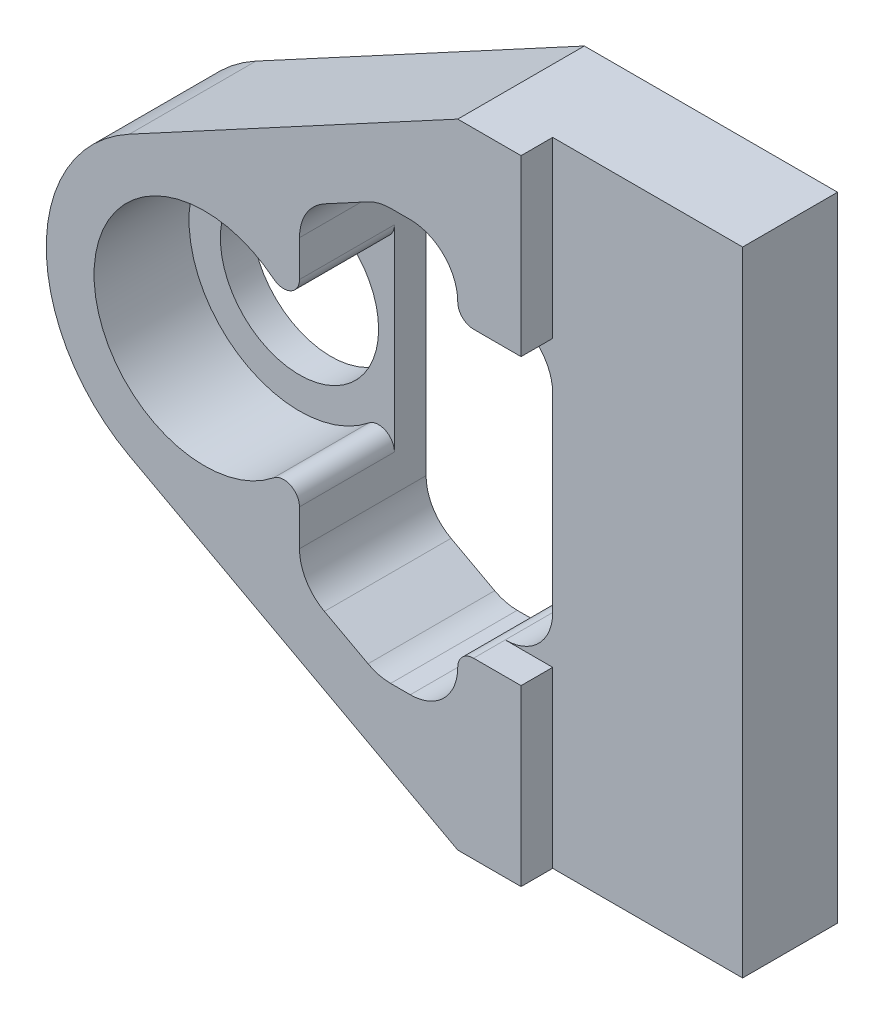
SolidWorks part; units mm, degrees
ref_plane "Front Plane" through (0, 0, 0) normal (0, 0, 1) x (1, 0, 0)
ref_plane "Top Plane" through (0, 0, 0) normal (0, 1, 0) x (1, 0, 0)
ref_plane "Right Plane" through (0, 0, 0) normal (1, 0, 0) x (0, 0, -1)
sketch "Sketch1" plane through (0, 0, 0) normal (0, 0, 1) x (1, 0, 0)
  line L0 (-2.3749, 4.4) -> (8, 10)
  line L1 (8, -10) -> (16, -10)
  line L2 (8, -10) -> (-2.3749, -4.4)
  line L3 (8, 10) -> (16, 10)
  line L4 (16, -10) -> (16, 10)
  circle A0 centre (0, 0) radius 2.5
  arc A1 (-2.3749, 4.4) -> (-2.3749, -4.4) centre (0, 0) ccw
  dimension "D5" = 5
  dimension "D2" = 5
  dimension "D1" = 16
  dimension "D3" = 8
  dimension "D4" = 10
  dimension "D6" = 10
extrude "Boss-Extrude1" add sketch "Sketch1" along normal blind 4
sketch "Sketch4" plane through (0, 0, 4) normal (0, 0, 1) x (1, 0, 0)
  circle A0 centre (0, 0) radius 3.49
  dimension "D1" = 6.98
extrude "Cut-Extrude1" cut sketch "Sketch4" against normal blind 3
sketch "Sketch5" plane through (0, 0, 4) normal (0, 0, 1) x (1, 0, 0)
  line L0 (8, -10) -> (16, -10) construction
  line L1 (16, 10) -> (10, 10)
  line L2 (16, 10) -> (16, -10)
  line L3 (16, -10) -> (10, -10)
  line L4 (10, 10) -> (10, -10)
  dimension "D1" = 6
extrude "Cut-Extrude2" cut sketch "Sketch5" against normal blind 1
sketch "Sketch6" plane through (0, 0, 4) normal (0, 0, 1) x (1, 0, 0)
  line L0 (3, 5.1506) -> (5.5, 6.5)
  line L1 (5.5, 6.5) -> (8, 6.5)
  line L2 (3, 5.1506) -> (3, -5.1506)
  line L3 (5.5, -6.5) -> (8, -6.5)
  line L4 (8, -4.5) -> (8, -6.5)
  line L5 (3, -5.1506) -> (5.5, -6.5)
  line L6 (8, 10) -> (-2.3749, 4.4) construction
  line L7 (8, -4.5) -> (10, -4.5)
  line L8 (10, 10) -> (10, -10) construction
  line L9 (10, -4.5) -> (10, 4.5)
  line L10 (10, 10) -> (10, -10) construction
  line L11 (10, 4.5) -> (8, 4.5)
  line L12 (8, 4.5) -> (8, 6.5)
  dimension "D1" = 3
  dimension "D2" = 5
  dimension "D3" = 6.5
  dimension "D4" = 13
  dimension "D5" = 2.5
  dimension "D6" = 9
extrude "Cut-Extrude3" cut sketch "Sketch6" against normal up to next
fillet "Fillet1" radius 0.5 2 edges at (3, 1.7833, 2.5) (3, -1.7833, 2.5)
fillet "Fillet2" radius 1.5 8 edges at (5.5, -6.5, 2) (3, -5.1506, 2) (5.5, 6.5, 2) (3, 5.1506, 2) (8, -6.5, 2) (10, -4.5, 1.5) (10, 4.5, 1.5) (8, 6.5, 2)
fillet "Fillet3" radius 0.5 2 edges at (8, -4.5, 2) (8, 4.5, 2)
